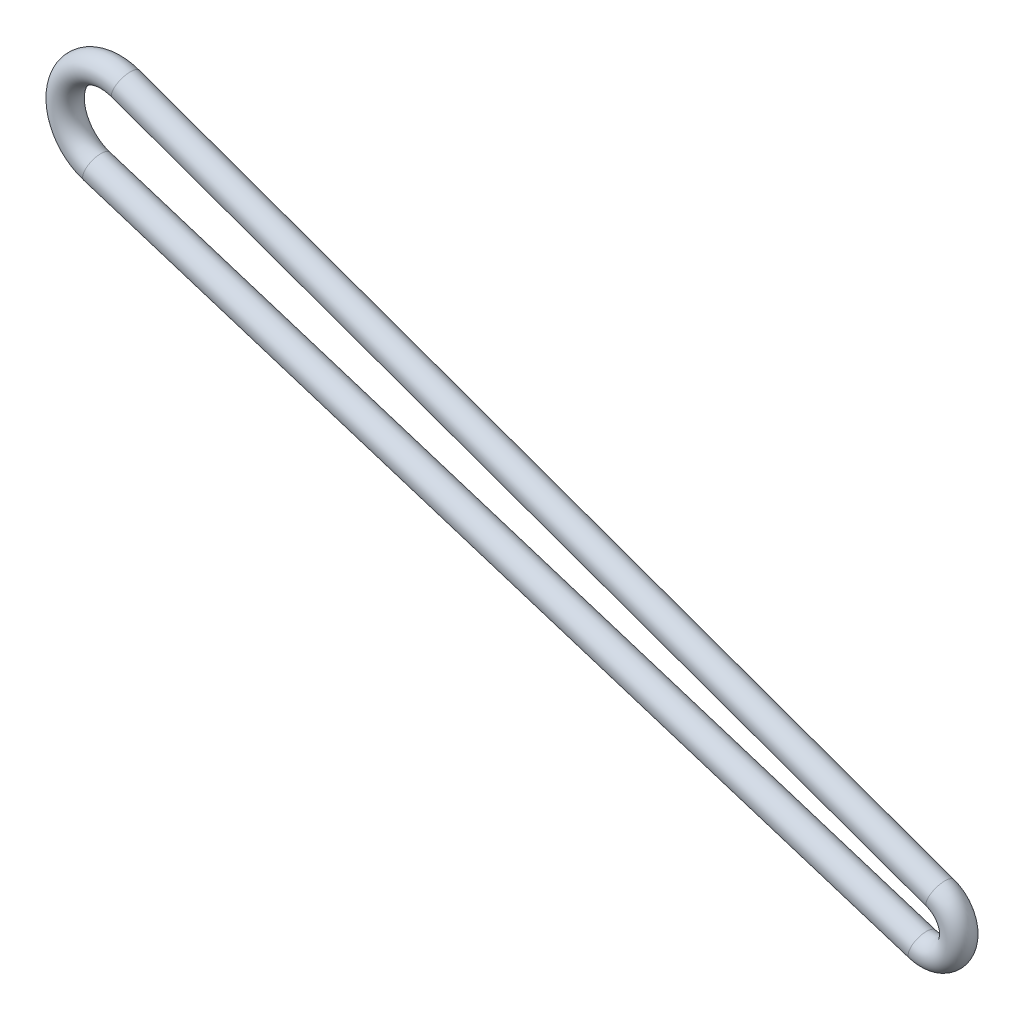
SolidWorks part; units mm, degrees
ref_plane "前视基准面" through (0, 0, 0) normal (0, 0, 1) x (1, 0, 0)
ref_plane "上视基准面" through (0, 0, 0) normal (0, 1, 0) x (1, 0, 0)
ref_plane "右视基准面" through (0, 0, 0) normal (1, 0, 0) x (0, 0, -1)
sketch "草图2" plane through (0, 0, 0) normal (0, 0, 1) x (1, 0, 0)
  line L0 (0, 0) -> (1, 0) construction
  line L1 (0, 0) -> (0, 1) construction
  line L2 (358.2392, 265.0888) -> (267.0674, 293.8986)
  line L3 (270.2687, 303.3702) -> (360.224, 270.9612)
  arc A0 (360.224, 270.9612) -> (358.2392, 265.0888) centre (359.1733, 268.0447) cw
  arc A1 (267.0674, 293.8986) -> (270.2687, 303.3702) centre (268.5739, 298.6662) cw
sweep "扫描19" add path "草图2" circular profile diameter 3 parameters "D3"=3
